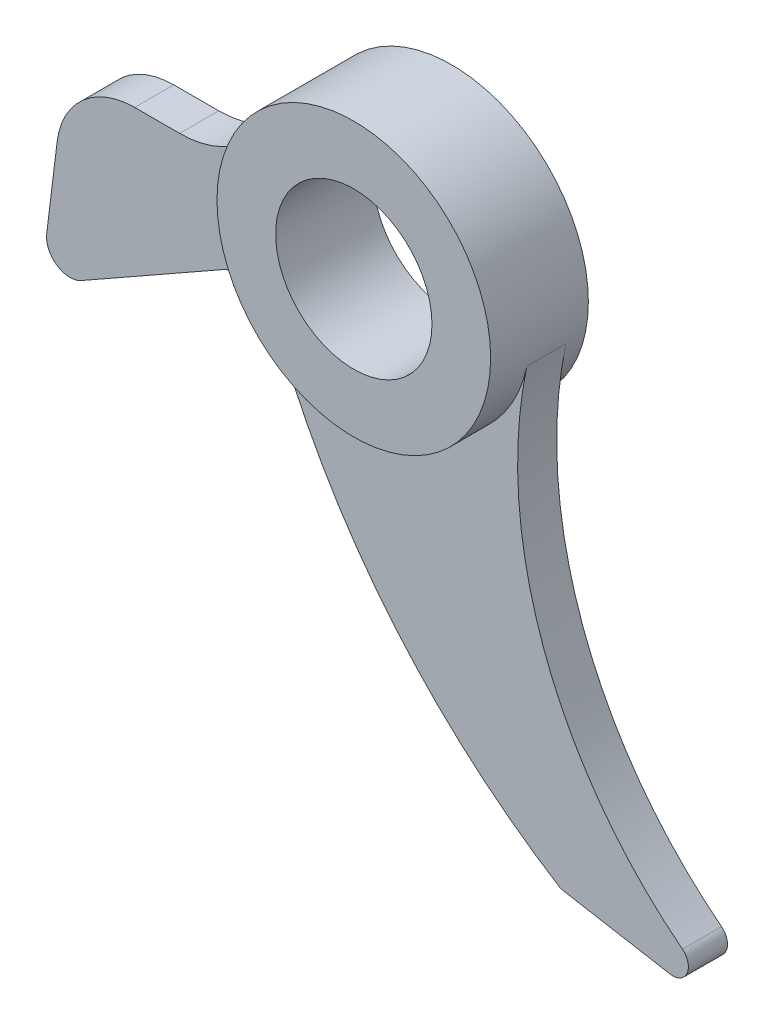
SolidWorks part; units mm, degrees
ref_plane "Ön Düzlem" through (0, 0, 0) normal (0, 0, 1) x (1, 0, 0)
ref_plane "Üst Düzlem" through (0, 0, 0) normal (0, 1, 0) x (1, 0, 0)
ref_plane "Sağ Düzlem" through (0, 0, 0) normal (1, 0, 0) x (0, 0, -1)
sketch "Çizim2" plane through (0, 0, 0) normal (0, 0, 1) x (1, 0, 0)
  line L0 (27.5928, 20.5375) -> (-81.7783, 20.5375)
  line L1 (27.5928, 20.5375) -> (85.8673, 20.5375)
  line L2 (-58.3002, 2.9749) -> (-60.9573, -18.6652)
  line L3 (-62.4072, 45.5375) -> (-62.4072, -30.4733) construction
  line L4 (-62.4072, -30.4733) -> (-52.0229, 54.0999) construction
  line L5 (27.5928, 20.5375) -> (-62.4072, -30.4733) construction
  line L6 (-51.685, -24.3961) -> (-15.9937, -4.1668)
  line L7 (70.0963, -97.9578) -> (98.4843, -102.9634)
  line L8 (60.4286, -105.6692) -> (113.8295, -105.6692) construction
  line L9 (70.0963, -97.9578) -> (70.0963, -97.7558)
  line L10 (101.646, -95.8756) -> (113.8295, -105.6692) construction
  line L11 (98.4843, -102.9634) -> (113.8295, -105.6692) construction
  line L12 (27.5928, 20.5375) -> (132.9521, -7.6934) construction
  circle A0 centre (27.5928, 20.5375) radius 20
  circle A1 centre (27.5928, 20.5375) radius 35
  arc A2 (-26.9507, 20.5375) -> (-4.2242, 35.1208) centre (-26.9507, 45.5375) ccw
  arc A3 (-38.4493, 20.5375) -> (-58.3002, 2.9749) centre (-38.4493, 0.5375) ccw
  arc A4 (-60.9573, -18.6652) -> (-51.685, -24.3961) centre (-55.002, -19.3964) ccw
  arc A5 (-1.0628, -12.8754) -> (-15.9937, -4.1668) centre (-11.0628, -12.8665) ccw
  arc A7 (-15.8647, -4.0949) -> (-15.8658, -4.0943) centre (-96.9538, -164.7951) ccw
  arc A8 (63.6131, 20.5375) -> (101.646, -95.8756) centre (169.4917, -9.2906) ccw
  arc A9 (98.4843, -102.9634) -> (101.646, -95.8756) centre (99.1789, -99.0242) ccw
  arc A10 (-55.8241, 10.4429) -> (-62.4072, 11.8586) centre (-96.9538, -164.7951) ccw
  arc A12 (-1.0628, -12.8754) -> (70.5462, -98.0372) centre (165.7648, 54.7156) ccw
  dimension "D1" = 7
  dimension "D3" = 40
  dimension "D2" = 70
  dimension "D4" = 25
  dimension "D5" = 20
  dimension "D6" = 6
  dimension "D8" = 4
  dimension "D9" = 110
  dimension "D10" = 28.388
  dimension "D11" = 10
  dimension "D7" = 10
  dimension "D12" = 15
  dimension "D13" = 90
extrude "Yükseklik-Ekstrüzyon6" add sketch "Çizim2" against normal blind 10 and the other way blind 15 contours L0 A1 L1 A0 | L1 A1 L0 A0 region at (-5.8375, 27.834, 0) region at (0.0928, 19.7549, 0)
extrude "Yükseklik-Ekstrüzyon7" add sketch "Çizim2<9>" against normal blind 5 and the other way blind 5 contours A5 A12 L7 A9 A8 A1 L0 A3 L2 A4 L6 | A2 L0 A1 region at (23.6616, -34.8811, 0) region at (-11.5511, 23.8024, 0)
sketch "Çizim2<9>" plane through (0, 0, 0) normal (0, 0, 1) x (1, 0, 0) same geometry as "Çizim2"
